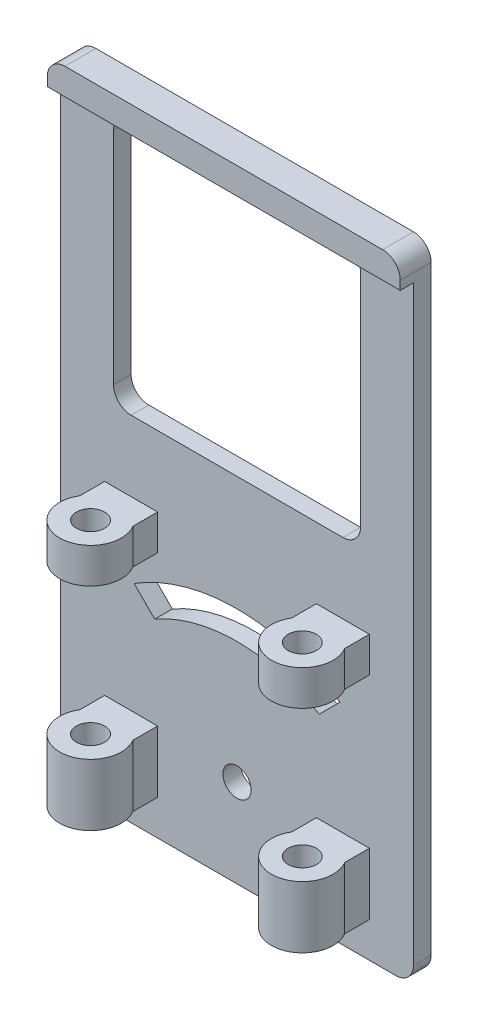
SolidWorks part; units mm, degrees
ref_plane "Front Plane" through (0, 0, 0) normal (0, 0, 1) x (1, 0, 0)
ref_plane "Top Plane" through (0, 0, 0) normal (0, 1, 0) x (1, 0, 0)
ref_plane "Right Plane" through (0, 0, 0) normal (1, 0, 0) x (0, 0, -1)
sketch "Sketch1" plane through (0, 0, 0) normal (0, 0, 1) x (1, 0, 0)
  line L1 (20, -20) -> (-20, -20)
  line L2 (20, -20) -> (20, 20)
  line L3 (20, 20) -> (-20, 20)
  line L4 (-20, -20) -> (-20, 20)
  line L5 (20, -20) -> (-20, 20) construction
  line L6 (20, 20) -> (-20, -20) construction
  point P0 (0, 0)
  dimension "D1" = 40
extrude "Boss-Extrude2" add sketch "Sketch1" along normal blind 2
sketch "Sketch2" plane through (0, 0, 2) normal (0, 0, 1) x (1, 0, 0)
  line L0 (-12, 0) -> (-12, 10) construction
  line L1 (0, 0) -> (-12, 0) construction
  line L2 (-15, 12) -> (-9, 12)
  line L3 (-15, 12) -> (-15, 8)
  line L4 (-15, 8) -> (-9, 8)
  line L5 (-9, 12) -> (-9, 8)
  line L6 (-15, 12) -> (-9, 8) construction
  line L7 (-15, 8) -> (-9, 12) construction
  point P1 (-12, 10)
  dimension "D1" = 10
  dimension "D2" = 4
  dimension "D3" = 6
  dimension "D4" = 12
extrude "Boss-Extrude5" add sketch "Sketch2" along normal blind 3
sketch "Sketch4" plane through (0, 12, 0) normal (0, 1, 0) x (1, 0, 0)
  line L1 (-9, -5) -> (-15, -5) construction
  circle A0 centre (-12, -6.6) radius 1.6
  circle A1 centre (-12, -6.6) radius 3.5
  point P9 (-12, -5)
  dimension "D1" = 3.2
  dimension "D2" = 7
  dimension "D3" = 1.6
extrude "Boss-Extrude6" add sketch "Sketch4" against normal blind 4
ref_plane "Plane2" through (0, 3, 0) normal (0, -1, 0) x (-1, 0, 0)
mirror "Mirror2" about plane through (0, 0, 0) normal (1, 0, 0) of "Boss-Extrude5", "Boss-Extrude6" second plane through (0, 3, 0) second plane normal (0, -1, 0)
sketch "Sketch6" plane through (0, 0, 2) normal (0, 0, 1) x (1, 0, 0)
  line L0 (-20, 20) -> (-15, 20)
  line L1 (20, 20) -> (-20, 20) construction
  line L2 (-15, 20) -> (-15, -20)
  line L3 (-20, -20) -> (20, -20) construction
  line L4 (-15, -20) -> (-20, -20)
  line L5 (-20, -20) -> (-20, 20)
  line L6 (20, 20) -> (15, 20)
  line L7 (15, 20) -> (15, -20)
  line L8 (15, -20) -> (20, -20)
  line L9 (20, -20) -> (20, 20)
  dimension "D1" = 5
  dimension "D2" = 5
  dimension "D4" = 5
extrude "Cut-Extrude1" [suppressed] cut sketch "Sketch6" against normal blind 3 contours L5 L0 L2 L4 | L9 L6 L7 L8
sketch "Sketch7" plane through (0, 0, 2) normal (0, 0, 1) x (1, 0, 0)
  line L0 (0, 0) -> (0, -15)
  line L1 (0, 0) -> (0, 7) construction
  line L2 (-8, 0) -> (8, 0) construction
  line L3 (9.3246, 1.3246) -> (11.6575, 3.6575)
  line L4 (-9.3246, 1.3246) -> (-11.6575, 3.6575)
  line L5 (-8, 0) -> (-9.3246, 1.3246) construction
  line L6 (8, 0) -> (9.3246, 1.3246) construction
  arc A0 (11.6575, 3.6575) -> (-11.6575, 3.6575) centre (0, -15) ccw
  arc A1 (9.3246, 1.3246) -> (-9.3246, 1.3246) centre (0, -15) ccw
  arc A2 (-9.3246, 1.3246) -> (9.3246, 1.3246) centre (0, -15) ccw construction
  arc A3 (-11.6575, 3.6575) -> (11.6575, 3.6575) centre (0, -15) ccw construction
  point P9 (0, 0)
  dimension "D1" = 15
  dimension "D2" = 7
  dimension "D3" = 3.2
  dimension "D4" = 8
  dimension "D5" = 45
  dimension "D6" = 45
extrude "Cut-Extrude2" cut sketch "Sketch7" against normal blind 2 contours A1 L3 A0 L4 region at (0, 4.477, 2)
sketch "Sketch8" plane through (0, 0, 0) normal (0, 0, -1) x (-1, 0, 0)
  line L0 (0, 0) -> (0, -10) construction
  circle A0 centre (0, -10) radius 1.6
  dimension "D1" = 10
  dimension "D2" = 3.2
extrude "Cut-Extrude3" cut sketch "Sketch8" against normal blind 2
sketch "Sketch18" plane through (0, 20, 0) normal (0, 1, 0) x (1, 0, 0)
  line L1 (20, -2) -> (14, -2)
  line L2 (20, -2) -> (20, 0)
  line L3 (20, 0) -> (14, 0)
  line L4 (20, 0) -> (-20, 0)
  line L5 (-20, 0) -> (-20, -2)
  line L6 (-20, -2) -> (20, -2)
  line L7 (20, -2) -> (20, 0)
  line L8 (20, 0) -> (-20, 0)
  line L9 (-20, 0) -> (-20, -2)
  line L10 (-20, -2) -> (20, -2)
  line L11 (20, -2) -> (20, 0)
  line L12 (14, -2) -> (14, 0)
  line L13 (-20, 0) -> (-14, 0)
  line L14 (-20, 0) -> (-20, -2)
  line L15 (-20, -2) -> (-14, -2)
  line L16 (-14, 0) -> (-14, -2)
  line M5 (20, 0) -> (-20, 0)
  line M6 (-20, 0) -> (-20, -2)
  line M7 (-20, -2) -> (20, -2)
  line M8 (20, -2) -> (20, 0)
  dimension "D2" = 6
  dimension "D3" = 6
  dimension "D1" = 0
extrude "Boss-Extrude10" add sketch "Sketch18" along normal blind 32 contours L12 M7 M8 M5 | L16 L8 M6 M7 region at (17, 20, 1) region at (-17, 20, 1)
sketch "Sketch19" plane through (0, 52, 0) normal (0, 1, 0) x (1, 0, 0)
  line L1 (-20, 0) -> (20, 0)
  line L2 (-20, 0) -> (-20, -3.5)
  line L3 (-20, -3.5) -> (20, -3.5)
  line L4 (-14, -2) -> (-14, 0)
  line L5 (-14, 0) -> (-20, 0)
  line L6 (-20, 0) -> (-20, -2)
  line L7 (-20, -2) -> (-14, -2)
  line L8 (-14, -2) -> (-14, 0)
  line L9 (-14, 0) -> (-20, 0)
  line L10 (-20, 0) -> (-20, -2)
  line L11 (-20, -2) -> (-14, -2)
  line L12 (20, 0) -> (20, -3.5)
  line M9 (-14, -2) -> (-14, 0)
  line M10 (-14, 0) -> (-20, 0)
  line M11 (-20, 0) -> (-20, -2)
  line M12 (-20, -2) -> (-14, -2)
  dimension "D2" = 3.5
  dimension "D3" = 40
  dimension "D1" = 0
extrude "Boss-Extrude11" add sketch "Sketch19" against normal blind 3 contours L12 L1 L2 L3 M9 M12 | M12 M9 M10 M11 region at (-17, 52, 1) region at (1.5937, 52, 1.8203)
fillet "Fillet1" radius 2 8 edges at (20, -20, 1) (-20, -20, 1) (-20, 52, 1.75) (20, 52, 1.75) (14, 20, 1) (-14, 20, 1) (-14, 49, 1) (14, 49, 1)
sketch "Sketch20" plane through (0, -6, 0) normal (0, -1, 0) x (1, 0, 0)
  line L3 (-9, 2) -> (-9, 4.7972)
  line L4 (-15, 4.7972) -> (-15, 2)
  line L5 (-15, 2) -> (-9, 2)
  line L6 (-9, 2) -> (-9, 4.7972)
  line L7 (-15, 4.7972) -> (-15, 2)
  line L8 (-15, 2) -> (-9, 2)
  line L9 (9, 4.7972) -> (9, 2)
  line L10 (9, 2) -> (15, 2)
  line L11 (15, 2) -> (15, 4.7972)
  line L12 (9, 4.7972) -> (9, 2)
  line L13 (9, 2) -> (15, 2)
  line L14 (15, 2) -> (15, 4.7972)
  circle A0 centre (-12, 6.6) radius 1.6 construction
  arc A1 (-9, 4.7972) -> (-15, 4.7972) centre (-12, 6.6) ccw
  arc A2 (-9, 4.7972) -> (-15, 4.7972) centre (-12, 6.6) ccw
  arc A3 (15, 4.7972) -> (9, 4.7972) centre (12, 6.6) ccw
  arc A4 (15, 4.7972) -> (9, 4.7972) centre (12, 6.6) ccw
  circle A5 centre (-12, 6.6) radius 1.6
  circle A6 centre (12, 6.6) radius 1.6 construction
  circle A7 centre (12, 6.6) radius 1.6
  dimension "D1" = 0
  dimension "D2" = 0
extrude "Boss-Extrude12" add sketch "Sketch20" along normal blind 10
sketch "Sketch21" plane through (0, 12, 0) normal (0, 1, 0) x (1, 0, 0)
  line L0 (9, -2) -> (9, -4.7972) construction
  line L1 (15, -4.7972) -> (15, -2) construction
  line L2 (15, -2) -> (9, -2) construction
  line L3 (-9, -4.7972) -> (-9, -2) construction
  line L4 (-9, -2) -> (-15, -2) construction
  line L5 (-15, -2) -> (-15, -4.7972) construction
  line L6 (9, -2) -> (9, -4.7972)
  line L7 (15, -4.7972) -> (15, -2)
  line L8 (15, -2) -> (9, -2)
  line L9 (-9, -4.7972) -> (-9, -2)
  line L10 (-9, -2) -> (-15, -2)
  line L11 (-15, -2) -> (-15, -4.7972)
  arc A0 (9, -4.7972) -> (15, -4.7972) centre (12, -6.6) ccw construction
  arc A1 (-15, -4.7972) -> (-9, -4.7972) centre (-12, -6.6) ccw construction
  circle A2 centre (-12, -6.6) radius 1.6 construction
  circle A3 centre (12, -6.6) radius 1.6 construction
  arc A4 (9, -4.7972) -> (15, -4.7972) centre (12, -6.6) ccw
  arc A5 (-15, -4.7972) -> (-9, -4.7972) centre (-12, -6.6) ccw
  circle A6 centre (-12, -6.6) radius 1.6
  circle A7 centre (12, -6.6) radius 1.6
sketch "Sketch22" plane through (0, -2, 0) normal (0, 1, 0) x (1, 0, 0)
  line L3 (9, -2) -> (9, -4.7972)
  line L4 (15, -4.7972) -> (15, -2)
  line L5 (15, -2) -> (9, -2)
  line L6 (9, -2) -> (9, -4.7972)
  line L7 (15, -4.7972) -> (15, -2)
  line L8 (15, -2) -> (9, -2)
  line L9 (-9, -4.7972) -> (-9, -2)
  line L10 (-9, -2) -> (-15, -2)
  line L11 (-15, -2) -> (-15, -4.7972)
  line L12 (-9, -4.7972) -> (-9, -2)
  line L13 (-9, -2) -> (-15, -2)
  line L14 (-15, -2) -> (-15, -4.7972)
  circle A0 centre (12, -6.6) radius 1.6 construction
  arc A1 (9, -4.7972) -> (15, -4.7972) centre (12, -6.6) ccw
  arc A2 (9, -4.7972) -> (15, -4.7972) centre (12, -6.6) ccw
  circle A3 centre (12, -6.6) radius 1.6
  circle A4 centre (-12, -6.6) radius 1.6 construction
  arc A5 (-15, -4.7972) -> (-9, -4.7972) centre (-12, -6.6) ccw
  arc A6 (-15, -4.7972) -> (-9, -4.7972) centre (-12, -6.6) ccw
  circle A7 centre (-12, -6.6) radius 1.6
  dimension "D1" = 0
  dimension "D2" = 0
extrude "Cut-Extrude4" cut sketch "Sketch22" against normal blind 7
